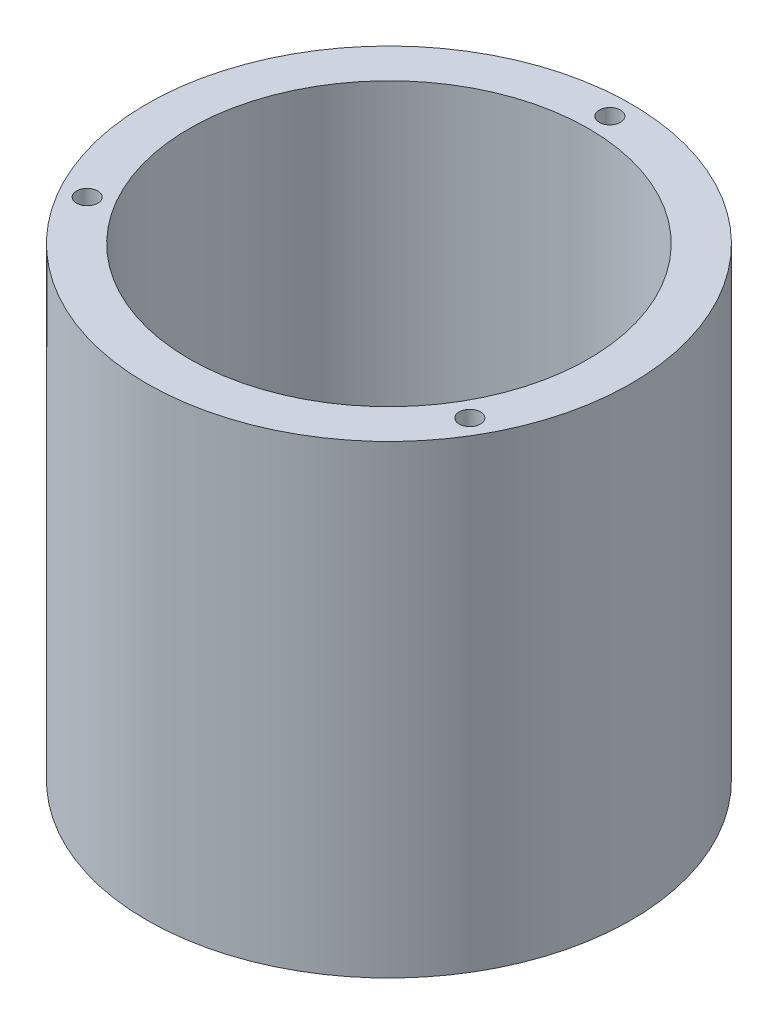
SolidWorks part; units mm, degrees
ref_plane "Front Plane" through (0, 0, 0) normal (0, 0, 1) x (1, 0, 0)
ref_plane "Top Plane" through (0, 0, 0) normal (0, 1, 0) x (1, 0, 0)
ref_plane "Right Plane" through (0, 0, 0) normal (1, 0, 0) x (0, 0, -1)
sketch "Sketch1" plane through (0, 0, 0) normal (0, 1, 0) x (1, 0, 0)
  circle A0 centre (0, 0) radius 45.5
  circle A2 centre (0, 0) radius 33.5
  dimension "D1" = 91
  dimension "D3" = 67
extrude "Boss-Extrude1" add sketch "Sketch1" along normal blind 4
sketch "Sketch2" plane through (0, 4, 0) normal (0, 1, 0) x (1, 0, 0)
  circle A0 centre (0, 0) radius 37.5
  circle A1 centre (0, 0) radius 45.5
  dimension "D1" = 91
  dimension "D2" = 75
extrude "Boss-Extrude2" add sketch "Sketch2" along normal blind 83.3
sketch "Sketch4" plane through (0, 87.3, 0) normal (0, 1, 0) x (1, 0, 0)
  line L0 (0, 0) -> (0, 41.5) construction
  circle A0 centre (0, 41.5) radius 2
  dimension "D1" = 41.5
  dimension "D2" = 4
extrude "Cut-Extrude1" cut sketch "Sketch4" against normal blind 6 contours A0
pattern_circular "CirPattern1" count 3 over 360 about axis through (0, 87.3, 0) along (0, 1, 0) of "Cut-Extrude1"
